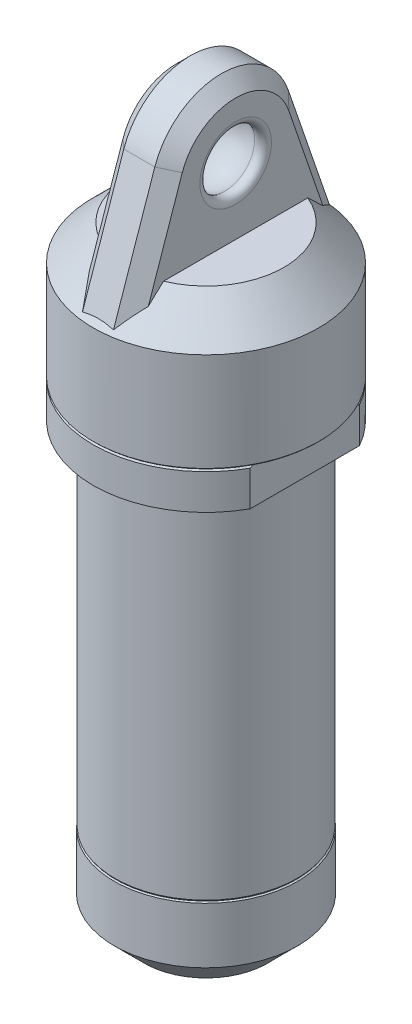
SolidWorks part; units mm, degrees
ref_plane "Front Plane" through (0, 0, 0) normal (0, 0, 1) x (1, 0, 0)
ref_plane "Top Plane" through (0, 0, 0) normal (0, 1, 0) x (1, 0, 0)
ref_plane "Right Plane" through (0, 0, 0) normal (1, 0, 0) x (0, 0, -1)
sketch "Sketch1" plane through (0, 0, 0) normal (1, 0, 0) x (0, 0, -1)
  line L0 (0, 0) -> (5.5251, 0)
  line L1 (5.5251, 0) -> (8, -2.4749)
  line L2 (8, -2.4749) -> (8, -9.45)
  line L5 (8, -9.65) -> (8, -12.15)
  line L6 (8, -12.15) -> (6.465, -12.15)
  line L7 (6.465, -12.15) -> (6.465, -37.05)
  line L8 (6.465, -37.05) -> (6.4, -37.15)
  line L9 (6.4, -37.15) -> (6.5, -37.215)
  line L10 (6.5, -37.215) -> (6.5, -41.1787)
  line L12 (4.3787, -43.3) -> (1.5, -43.3)
  line L13 (1.5, -43.3) -> (1.5, -10)
  line L14 (1.5, -10) -> (0, -10)
  line L15 (0, -10) -> (0, 0)
  line L16 (8, -9.65) -> (7.9, -9.55)
  line L17 (7.9, -9.55) -> (8, -9.45)
  line L19 (4.3787, -43.3) -> (6.5, -41.1787)
  dimension "D1" = 1.5
  dimension "D2" = 6.465
  dimension "D3" = 6.5
  dimension "D4" = 37.15
  dimension "D5" = 8
  dimension "D6" = 12.15
  dimension "D7" = 2.5
  dimension "D8" = 8
  dimension "D9" = 45
  dimension "D10" = 0.1
  dimension "D11" = 45
  dimension "D12" = 3.5
  dimension "D13" = 43.3
  dimension "D14" = 45
  dimension "D15" = 3
  dimension "D16" = 0.1
  dimension "D17" = 10
revolve "Revolve1" add sketch "Sketch1" angle 360 about L15
sketch "Sketch2" plane through (0, 0, 0) normal (1, 0, 0) x (0, 0, -1)
  line L0 (-7.75, -2.4749) -> (-4.729, 6.3237)
  line L1 (4.729, 6.3237) -> (7.75, -2.4749)
  line L2 (-7.75, -2.4749) -> (7.75, -2.4749)
  line L3 (5.5251, 0) -> (-5.5251, 0) construction
  line L4 (8, -2.4749) -> (-8, -2.4749) construction
  arc A0 (-4.729, 6.3237) -> (4.729, 6.3237) centre (0, 4.7) cw
  point P7 (0, 9.7)
  dimension "D1" = 5
  dimension "D2" = 9.7
  dimension "D3" = 0.25
extrude "Boss-Extrude1" add sketch "Sketch2" along normal mid plane 4.2
chamfer "Chamfer1" distance 1 angle 45 6 edges at (-2.1, 1.9244, 6.2395) (2.1, 1.9244, 6.2395) (-2.1, 1.9244, -6.2395) (-2.1, 9.7, 0) (2.1, 1.9244, -6.2395) (2.1, 9.7, 0)
sketch "Sketch3" plane through (0, -12.15, 0) normal (0, -1, 0) x (1, 0, 0)
  line L0 (-7, 3.873) -> (-7, -3.873)
  line L1 (0, -55) -> (0, 55) construction
  line L2 (7, 3.873) -> (7, -3.873)
  arc A0 (-7, 3.873) -> (-7, -3.873) centre (0, 0) ccw
  circle A1 centre (0, 0) radius 8
  arc A2 (7, -3.873) -> (7, 3.873) centre (0, 0) ccw
  dimension "D2" = 14
  dimension "D1" = 0
ref_plane "Plane1" through (0, -9.55, 0) normal (0, 1, 0) x (1, 0, 0)
extrude "Cut-Extrude1" cut sketch "Sketch3" against normal up to surface (2.6 mm away) up to plane "Plane1"
sketch "Sketch4" plane through (0, 0, 0) normal (1, 0, 0) x (0, 0, -1)
  line L0 (0, 7.2) -> (0, 2.2) construction
  circle A0 centre (0, 4.7) radius 2.5
  arc A1 (3.7832, 5.999) -> (-3.7832, 5.999) centre (0, 4.7) ccw construction
  dimension "D1" = 5
revolve "Cut-Revolve3" cut sketch "Sketch4" angle 360 about L0 region at (0, 4.7, 1.061)
fillet "Fillet1" radius 0.5 2 edges at (2.1, 4.7, 1.3565) (-2.1, 4.7, 1.3565)
